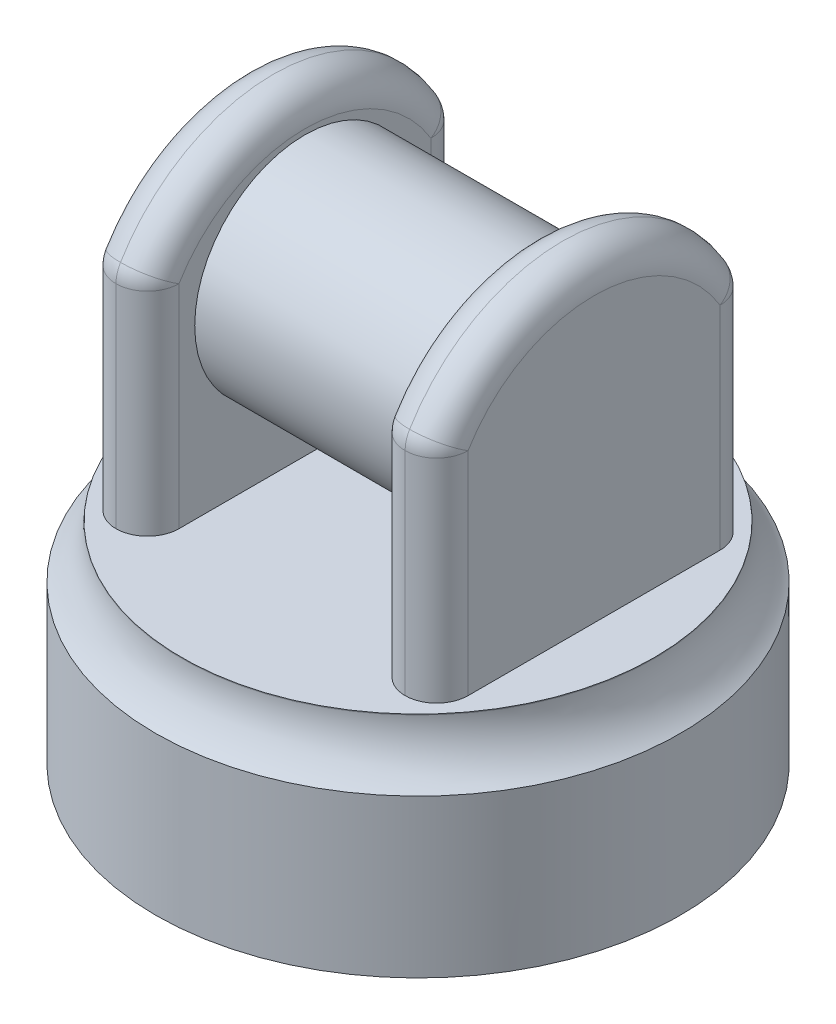
SolidWorks part; units mm, degrees
ref_plane "Piano frontale" through (0, 0, 0) normal (0, 0, 1) x (1, 0, 0)
ref_plane "Piano superiore" through (0, 0, 0) normal (0, 1, 0) x (1, 0, 0)
ref_plane "Piano destro" through (0, 0, 0) normal (1, 0, 0) x (0, 0, -1)
sketch "Schizzo1" plane through (0, 0, 0) normal (0, 1, 0) x (1, 0, 0)
  circle A0 centre (0, 0) radius 25
  dimension "D1" = 50
extrude "Estrusione-Estrusione1" add sketch "Schizzo1" along normal blind 15
sketch "Schizzo2" plane through (0, 15, 0) normal (0, 1, 0) x (1, 0, 0)
  circle A0 centre (0, 0) radius 22.5
  dimension "D1" = 45
extrude "Estrusione-Estrusione2" add sketch "Schizzo2" along normal blind 5
fillet "Raccordo1" radius 6.1 1 edges at (0, 15, 22.5)
sketch "Schizzo3" plane through (0, 20, 0) normal (0, 1, 0) x (1, 0, 0)
  line L0 (0, -15) -> (0, 15) construction
  line L1 (-16.7705, 15) -> (16.7705, 15) construction
  line L2 (-16.7705, -15) -> (16.7705, -15) construction
  line L3 (-16.7705, -15) -> (-16.7705, 15)
  line L4 (-16.7705, 15) -> (-10.7705, 15)
  line L5 (-10.7705, 15) -> (-10.7705, -15)
  line L6 (-10.7705, -15) -> (-16.7705, -15)
  line L7 (16.7705, 15) -> (16.7705, -15)
  line L8 (16.7705, -15) -> (10.7705, -15)
  line L9 (10.7705, -15) -> (10.7705, 15)
  line L10 (10.7705, 15) -> (16.7705, 15)
  circle A0 centre (0, 0) radius 22.5 construction
  point P4 (0, 0)
  point P9 (0, 15)
  point P12 (0, -15)
  dimension "D1" = 30
  dimension "D2" = 6
extrude "Estrusione-Estrusione3" add sketch "Schizzo3" along normal blind 30
sketch "Schizzo4" plane through (16.7705, 0, 0) normal (1, 0, 0) x (0, 0, -1)
  line L0 (-15, 50) -> (-15, 20) construction
  line L1 (15, 50) -> (15, 20) construction
  line L6 (-15, 20) -> (15, 20)
  line L7 (15, 20) -> (15, 50)
  line L8 (15, 50) -> (-15, 50)
  line L9 (-15, 50) -> (-15, 20)
  line L11 (15, 41) -> (15, 50)
  line L12 (15, 50) -> (-15, 50)
  line L13 (-15, 50) -> (-15, 41)
  arc A0 (-15, 41) -> (15, 41) centre (0, 33) cw
  point P9 (0, 0)
  line M7 (15, 20) -> (15, 50)
  line M8 (15, 50) -> (-15, 50)
  line M9 (-15, 50) -> (-15, 20)
  dimension "D3" = 17
  dimension "D2" = 9
  dimension "D1" = 0
extrude "Taglio-Estrusione1" cut sketch "Schizzo4" against normal through all contours A0 L12 M9 | A0 M8 M7
fillet "Raccordo2" radius 3 12 edges at (-16.7705, 50, 0) (-10.7705, 50, 0) (10.7705, 50, 0) (16.7705, 50, 0) (10.7705, 30.5, -15) (16.7705, 30.5, -15) (-10.7705, 30.5, -15) (-16.7705, 30.5, -15) (16.7705, 30.5, 15) (10.7705, 30.5, 15) (-10.7705, 30.5, 15) (-16.7705, 30.5, 15)
sketch "Schizzo5" plane through (10.7705, 0, 0) normal (-1, 0, 0) x (0, 0, 1)
  circle A0 centre (0, 36) radius 10.5
  point P2 (0, 0)
  dimension "D1" = 21
  dimension "D2" = 36
extrude "Estrusione-Estrusione4" add sketch "Schizzo5" along normal up to next
